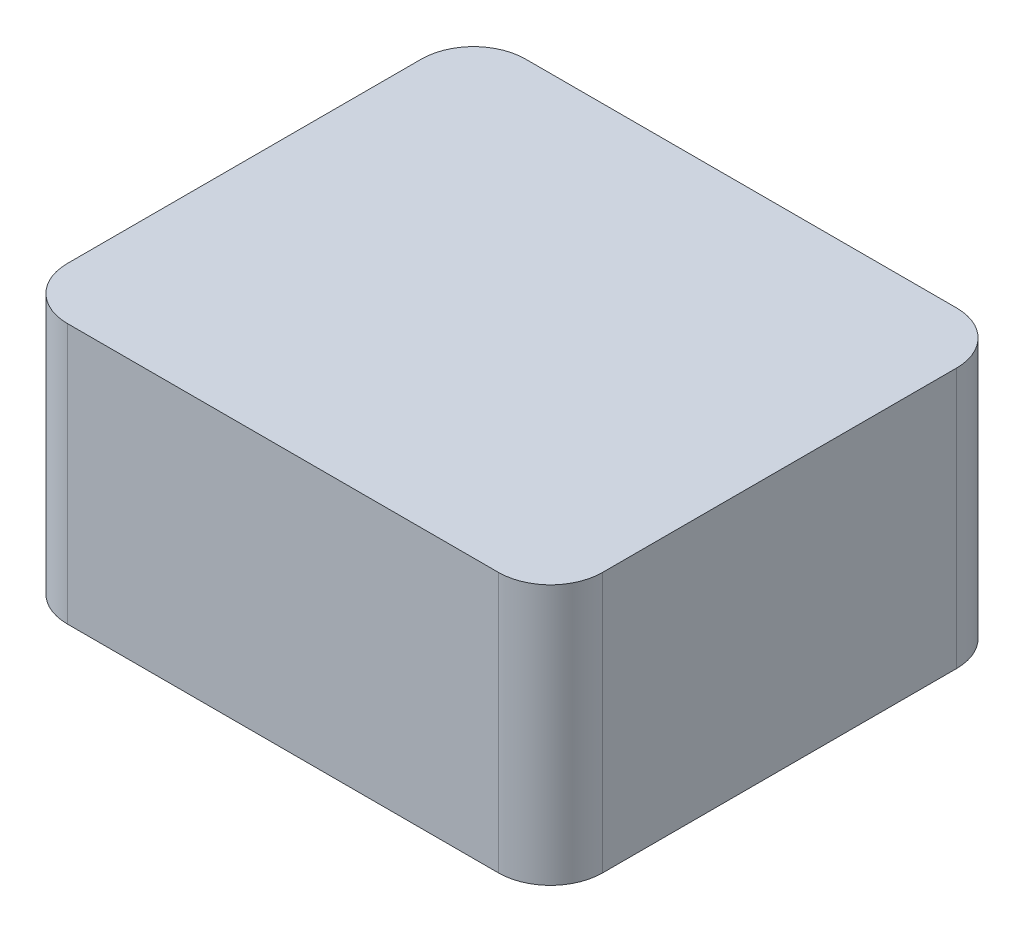
SolidWorks part; units mm, degrees
ref_plane "Front Plane" through (0, 0, 0) normal (0, 0, 1) x (1, 0, 0)
ref_plane "Top Plane" through (0, 0, 0) normal (0, 1, 0) x (1, 0, 0)
ref_plane "Right Plane" through (0, 0, 0) normal (1, 0, 0) x (0, 0, -1)
sketch "Sketch1" plane through (0, 0, 0) normal (0, 1, 0) x (1, 0, 0)
  line L1 (6.5278, -5.588) -> (-6.5278, -5.588)
  line L2 (6.5278, -5.588) -> (6.5278, 5.588)
  line L3 (6.5278, 5.588) -> (-6.5278, 5.588)
  line L4 (-6.5278, -5.588) -> (-6.5278, 5.588)
  line L5 (0, 5.588) -> (0, -5.588) construction
  line L6 (6.5278, 0) -> (-6.5278, 0) construction
  point P0 (0, 0)
  dimension "D1" = 11.176
  dimension "D2" = 13.0556
extrude "Boss-Extrude1" add sketch "Sketch1" along normal blind 6.35
fillet "Fillet1" radius 1.27 4 edges at (6.5278, 3.175, 5.588) (6.5278, 3.175, -5.588) (-6.5278, 3.175, -5.588) (-6.5278, 3.175, 5.588)
